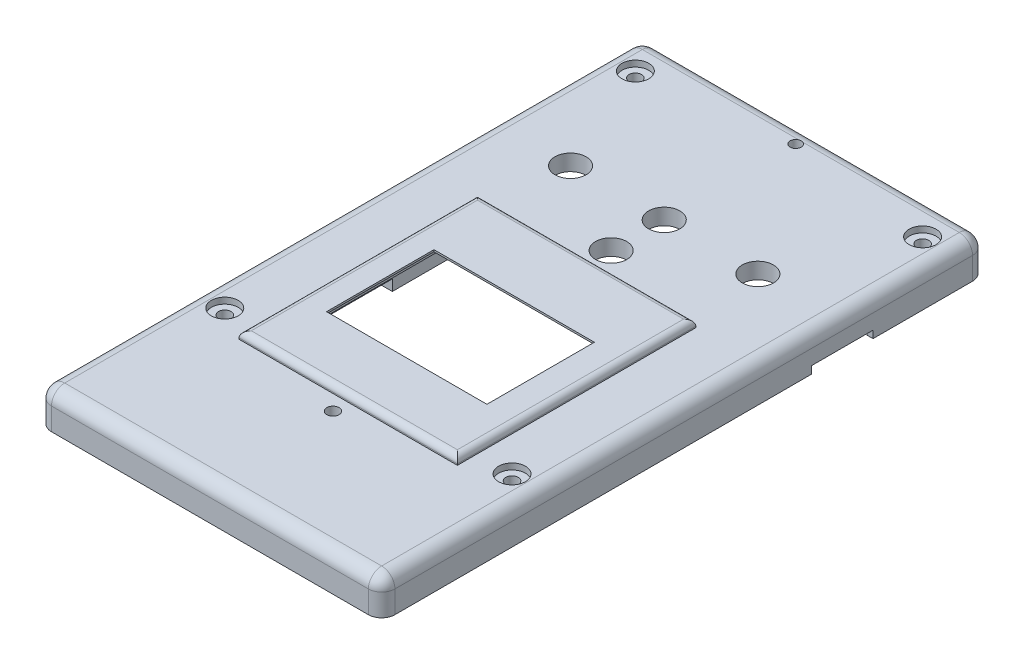
SolidWorks part; units mm, degrees
ref_plane "Face" through (0, 0, 0) normal (0, 0, 1) x (1, 0, 0)
ref_plane "Dessus" through (0, 0, 0) normal (0, 1, 0) x (1, 0, 0)
ref_plane "Droite" through (0, 0, 0) normal (1, 0, 0) x (0, 0, -1)
sketch "Sketch1" plane through (0, 0, 0) normal (0, 1, 0) x (1, 0, 0)
  line L0 (0, -49.53) -> (0, 0) construction
  line L1 (27.94, -49.53) -> (-27.94, -49.53)
  line L2 (27.94, -49.53) -> (27.94, 48.768)
  line L3 (27.94, 48.768) -> (-27.94, 48.768)
  line L4 (-27.94, -49.53) -> (-27.94, 48.768)
  point P0 (0, 0)
  dimension "D1" = 55.88
  dimension "D2" = 49.53
  dimension "D3" = 48.768
extrude "Boss-Extrude1" add sketch "Sketch1" along normal blind 4.99
fillet "Fillet1" radius 2.159 8 edges at (0, 4.99, 49.53) (27.94, 4.99, 0.381) (0, 4.99, -48.768) (-27.94, 4.99, 0.381) (-27.94, 2.495, -48.768) (27.94, 2.495, -48.768) (27.94, 2.495, 49.53) (-27.94, 2.495, 49.53)
sketch "Sketch3" plane through (0, 0, 0) normal (0, -1, 0) x (1, 0, 0)
  line L1 (21.6281, -38.862) -> (-20.4089, -38.862)
  line L2 (21.6281, -38.862) -> (21.6281, 26.576)
  line L3 (21.6281, 26.576) -> (-20.4089, 26.576)
  line L4 (-20.4089, -38.862) -> (-20.4089, 26.576)
  line L5 (21.6281, -38.862) -> (-20.4089, 26.576) construction
  line L6 (21.6281, 26.576) -> (-20.4089, -38.862) construction
  point P0 (0.6096, -6.143)
  dimension "D1" = 42.037
  dimension "D2" = 26.576
  dimension "D3" = 38.862
  dimension "D4" = 0.6096
sketch "Sketch7" plane through (0, 0, 0) normal (0, -1, 0) x (1, 0, 0)
  line L6 (-25.781, -47.752) -> (25.781, -47.752)
  line L9 (26.924, 47.371) -> (26.924, -46.609)
  line L10 (-26.924, -46.609) -> (-26.924, 47.371)
  line L11 (-25.781, 48.514) -> (25.781, 48.514)
  line L12 (26.924, 47.371) -> (26.924, -46.609)
  line L13 (-26.924, -46.609) -> (-26.924, 47.371)
  line L14 (-25.781, 48.514) -> (25.781, 48.514)
  arc A9 (25.781, -47.752) -> (26.924, -46.609) centre (25.781, -46.609) ccw
  arc A16 (25.781, -47.752) -> (26.924, -46.609) centre (25.781, -46.609) ccw
  arc A17 (-26.924, -46.609) -> (-25.781, -47.752) centre (-25.781, -46.609) ccw
  arc A18 (-26.924, -46.609) -> (-25.781, -47.752) centre (-25.781, -46.609) ccw
  arc A19 (-25.781, 48.514) -> (-26.924, 47.371) centre (-25.781, 47.371) ccw
  arc A20 (-25.781, 48.514) -> (-26.924, 47.371) centre (-25.781, 47.371) ccw
  arc A21 (26.924, 47.371) -> (25.781, 48.514) centre (25.781, 47.371) ccw
  arc A22 (26.924, 47.371) -> (25.781, 48.514) centre (25.781, 47.371) ccw
  dimension "D1" = 1.016
  dimension "D2" = 1.016
extrude "Cut-Extrude4" cut sketch "Sketch7" against normal blind 0.5874
sketch "Sketch8" plane through (0, 0, 0) normal (0, -1, 0) x (1, 0, 0)
  line L0 (27.94, 47.371) -> (27.94, -46.609) construction
  line L2 (26.924, -46.609) -> (26.924, 47.371) construction
  line L3 (-25.781, -47.752) -> (25.781, -47.752) construction
  line L4 (26.924, -46.609) -> (26.924, -40.386)
  line L5 (21.717, -47.752) -> (25.781, -47.752)
  line L6 (21.717, -47.752) -> (21.717, -40.386)
  line L7 (21.717, -40.386) -> (26.924, -40.386)
  circle A0 centre (23.4188, -43.006) radius 0.889
  arc A1 (25.781, -47.752) -> (26.924, -46.609) centre (25.781, -46.609) ccw construction
  arc A2 (25.781, -47.752) -> (26.924, -46.609) centre (25.781, -46.609) ccw
  dimension "D3" = 1.778
  dimension "D1" = 4.5212
  dimension "D2" = 43.006
  dimension "D4" = 6.223
  dimension "D5" = 40.386
sketch "Sketch9" plane through (0, 0, 0) normal (0, -1, 0) x (1, 0, 0)
  line L0 (-26.924, 47.371) -> (-26.924, -46.609) construction
  line L1 (-25.781, -47.752) -> (25.781, -47.752) construction
  line L2 (-26.924, -40.005) -> (-26.924, -46.609)
  line L3 (-25.781, -47.752) -> (-20.447, -47.752)
  line L4 (-20.447, -47.752) -> (-20.447, -40.005)
  line L5 (-20.447, -40.005) -> (-26.924, -40.005)
  line L6 (-27.94, -46.609) -> (-27.94, 47.371) construction
  arc A0 (-26.924, -46.609) -> (-25.781, -47.752) centre (-25.781, -46.609) ccw construction
  arc A1 (-26.924, -46.609) -> (-25.781, -47.752) centre (-25.781, -46.609) ccw
  circle A2 centre (-23.3172, -43.006) radius 0.889
  dimension "D5" = 1.778
  dimension "D1" = 7.493
  dimension "D2" = 43.006
  dimension "D3" = 3.6068
  dimension "D4" = 40.005
sketch "Sketch10" plane through (0, 0, 0) normal (0, -1, 0) x (1, 0, 0)
  line L0 (-27.94, -46.609) -> (-27.94, 47.371) construction
  line L1 (-26.924, 47.371) -> (-26.924, -46.609) construction
  line L2 (-26.924, 17.78) -> (-20.447, 17.78)
  line L3 (-26.924, 17.78) -> (-26.924, 26.67)
  line L4 (-26.924, 26.67) -> (-20.447, 26.67)
  line L5 (-20.447, 17.78) -> (-20.447, 26.67)
  circle A0 centre (-23.3172, 23.796) radius 0.889
  dimension "D6" = 1.778
  dimension "D1" = 4.6228
  dimension "D2" = 23.796
  dimension "D3" = 6.477
  dimension "D4" = 26.67
  dimension "D5" = 17.78
sketch "Sketch11" plane through (0, 0, 0) normal (0, -1, 0) x (1, 0, 0)
  line L0 (26.924, -46.609) -> (26.924, 47.371) construction
  line L1 (26.924, 27.686) -> (21.7502, 27.686)
  line L2 (26.924, 27.686) -> (26.924, 20.32)
  line L3 (26.924, 20.32) -> (21.7502, 20.32)
  line L4 (21.7502, 27.686) -> (21.7502, 20.32)
  circle A0 centre (23.4188, 23.796) radius 0.889
  dimension "D6" = 1.778
  dimension "D1" = 23.796
  dimension "D2" = 23.4188
  dimension "D3" = 27.686
  dimension "D4" = 20.32
  dimension "D5" = 21.7502
sketch "Sketch12" plane through (0, 0.5874, 0) normal (0, -1, 0) x (1, 0, 0)
  line L0 (26.924, -38.1) -> (19.812, -38.1)
  line L1 (-26.924, 27.94) -> (-16.28, 27.94)
  line L3 (-26.924, 13.7274) -> (-16.28, 13.7274)
  line L4 (26.924, -46.609) -> (26.924, 47.371)
  line L5 (25.781, 48.514) -> (-25.781, 48.514)
  line L6 (-26.924, 47.371) -> (-26.924, -46.609)
  line L7 (-25.781, -47.752) -> (25.781, -47.752)
  line L8 (26.924, -38.1) -> (26.924, -17.145)
  line L9 (25.781, 48.514) -> (8.5725, 48.514)
  line L10 (-26.924, 47.371) -> (-26.924, 27.94)
  line L11 (-19.812, -47.752) -> (19.812, -47.752)
  line L12 (-16.28, 27.94) -> (-16.28, 13.7274)
  line L13 (26.924, 27.94) -> (19.812, 27.94)
  line L17 (19.812, -38.1) -> (19.812, -47.752)
  line L18 (-26.924, -38.1) -> (-19.812, -38.1)
  line L19 (-19.812, -38.1) -> (-19.812, -47.752)
  line L20 (-26.924, 3.429) -> (-16.28, 3.429)
  line L21 (-16.28, 3.429) -> (-16.28, -17.145)
  line L22 (-16.28, -17.145) -> (-26.924, -17.145)
  line L25 (19.812, -17.145) -> (26.924, -17.145)
  line L26 (0, 44.704) -> (0, 0) construction
  line L28 (8.5725, 48.514) -> (8.5725, 44.704)
  line L29 (8.5725, 44.704) -> (-8.5725, 44.704)
  line L30 (-8.5725, 48.514) -> (-8.5725, 44.704)
  line L31 (0, 0) -> (0, -47.752) construction
  line L36 (-8.5725, 48.514) -> (-25.781, 48.514)
  line L37 (26.924, 27.94) -> (26.924, 47.371)
  line L38 (-26.924, 13.7274) -> (-26.924, 3.429)
  line L39 (-26.924, -17.145) -> (-26.924, -38.1)
  line L40 (26.924, -3.275) -> (26.924, 12.725)
  line L41 (19.812, -17.145) -> (19.812, -11.275)
  line L42 (19.812, -11.275) -> (22.346, -11.275)
  line L43 (22.346, -11.275) -> (22.346, -3.275)
  line L44 (22.346, -3.275) -> (26.924, -3.275)
  line L45 (19.812, 27.94) -> (19.812, 20.725)
  line L46 (19.812, 20.725) -> (22.346, 20.725)
  line L47 (22.346, 20.725) -> (22.346, 12.725)
  line L48 (22.346, 12.725) -> (26.924, 12.725)
  arc A4 (25.781, -47.752) -> (26.924, -46.609) centre (25.781, -46.609) ccw
  arc A5 (26.924, 47.371) -> (25.781, 48.514) centre (25.781, 47.371) ccw
  arc A6 (-25.781, 48.514) -> (-26.924, 47.371) centre (-25.781, 47.371) ccw
  arc A7 (-26.924, -46.609) -> (-25.781, -47.752) centre (-25.781, -46.609) ccw
  arc A9 (26.924, 47.371) -> (25.781, 48.514) centre (25.781, 47.371) ccw
  arc A10 (-25.781, 48.514) -> (-26.924, 47.371) centre (-25.781, 47.371) ccw
  line M33 (26.924, -46.609) -> (26.924, 47.371)
  arc M34 (26.924, 47.371) -> (25.781, 48.514) centre (25.781, 47.371) ccw
  line M35 (25.781, 48.514) -> (-25.781, 48.514)
  arc M36 (-25.781, 48.514) -> (-26.924, 47.371) centre (-25.781, 47.371) ccw
  line M37 (-26.924, 47.371) -> (-26.924, -46.609)
  line M39 (-25.781, -47.752) -> (25.781, -47.752)
  dimension "D2" = 12.725
  dimension "D3" = 17.145
  dimension "D4" = 3.81
  dimension "D5" = 27.94
  dimension "D6" = 14.2126
  dimension "D7" = 3.429
  dimension "D8" = 17.145
  dimension "D9" = 38.1
  dimension "D10" = 39.624
  dimension "D11" = 16.28
  dimension "D12" = 4.578
  dimension "D13" = 32
  dimension "D14" = 20.725
  dimension "D15" = 16
  dimension "D1" = 0
extrude "Cut-Extrude5" cut sketch "Sketch12" against normal blind 1.778 contours L17 L0 L25 L41 L48 L13 L28 L29 L30 L1 L12 L3 L20 L21 L22 L18 L19 M39 M33 M34 M35 M36 M37 region at (0.9045, 0.5874, 0.4828)
fillet "Fillet4" radius 1.016 11 edges at (26.924, 2.3654, 37.6555) (26.5892, 2.3654, 48.1792) (-26.924, 2.3654, 37.6555) (-26.5892, 2.3654, 48.1792) (0, 2.3654, -47.752) (-26.924, 2.3654, 8.5782) (-26.924, 2.3654, -27.6225) (26.924, 2.3654, -27.6225) (26.924, 2.3654, 4.725) (17.1767, 2.3654, 48.514) (-17.1767, 2.3654, 48.514)
hole_wizard "Chambrage pour vis à tête ronde à 6 pans creux #11" positions "Sketch13" profile "Sketch14" counterbore size "#1" standard "Ansi Inch"
sketch "Sketch13" plane through (0, 4.99, 0) normal (0, 1, 0) x (1, 0, 0)
  point P0 (-23.3172, -23.796)
  point P3 (23.4188, -23.796)
  point P6 (23.4188, 43.006)
  point P9 (-23.3172, 43.006)
sketch "Sketch14" plane through (-23.3172, 4.99, 23.796) normal (1, 0, 0) x (0, 0, 1)
  line L0 (0, 0) -> (0, 6.6105)
  line L1 (0, 6.6105) -> (1.016, 6)
  line L2 (1.016, 6) -> (1.016, 0.9906)
  line L3 (1.016, 0.9906) -> (2.1844, 0.9906)
  line L4 (2.1844, 0.9906) -> (2.1844, 0)
  line L5 (2.1844, 0) -> (0, 0)
  line L10 (0, 6.6105) -> (-1.016, 6) construction
  line L11 (0, -6.35) -> (0, 107.95) construction
  dimension "Diamètre du perçage" = 2.032
  dimension "Profondeur du perçage" = 6
  dimension "Diamètre du chambrage" = 4.3688
  dimension "Profondeur du chambrage" = 0.9906
  dimension "Angle de pointe" = 118
sketch "Sketch15" plane through (0, 2.3654, 0) normal (0, -1, 0) x (1, 0, 0)
  line L0 (0, 0) -> (0, -15.748) construction
  line L1 (0, -15.748) -> (0, -24.384) construction
  line L2 (0, -24.384) -> (-15.24, -24.384) construction
  line L3 (0, -24.384) -> (15.24, -24.384) construction
  circle A0 centre (0, -24.384) radius 2.54
  circle A1 centre (-15.24, -24.384) radius 2.54
  circle A2 centre (15.24, -24.384) radius 2.54
  circle A3 centre (0, -15.748) radius 2.54
  dimension "D4" = 5.08
  dimension "D1" = 24.384
  dimension "D2" = 15.748
  dimension "D3" = 30.48
extrude "Cut-Extrude6" cut sketch "Sketch15" against normal through all
sketch "Sketch16" plane through (0, 0.5874, 0) normal (0, 1, 0) x (1, 0, 0)
  line L0 (-25.781, -48.514) -> (-8.5725, -48.514) construction
  line L1 (16.424, -25.764) -> (-16.424, -25.764)
  line L2 (16.424, -25.764) -> (16.424, 11.236)
  line L3 (16.424, 11.236) -> (-16.424, 11.236)
  line L4 (-16.424, -25.764) -> (-16.424, 11.236)
  line L5 (26.924, 46.609) -> (26.924, -47.371) construction
  point P9 (0, 11.236)
  dimension "D1" = 22.75
  dimension "D2" = 10.5
  dimension "D3" = 37
extrude "Cut-Extrude7" cut sketch "Sketch16" along normal blind 4.2
sketch "Sketch17" plane through (0, 0, 0) normal (0, -1, 0) x (1, 0, 0)
  line L0 (-25.781, -47.752) -> (25.781, -47.752) construction
  line L1 (26.924, -46.609) -> (26.924, 47.371) construction
  line L2 (25.781, 48.514) -> (-25.781, 48.514) construction
  line L3 (-26.924, 47.371) -> (-26.924, -46.609) construction
  line L4 (-27.94, 47.371) -> (-27.94, -46.609)
  line L5 (-25.781, -48.768) -> (25.781, -48.768)
  line L6 (27.94, -46.609) -> (27.94, 47.371)
  line L7 (25.781, 49.53) -> (-25.781, 49.53)
  line L8 (-27.94, 47.371) -> (-27.94, -46.609)
  line L9 (-25.781, -48.768) -> (25.781, -48.768)
  line L10 (27.94, -46.609) -> (27.94, 47.371)
  line L11 (25.781, 49.53) -> (-25.781, 49.53)
  line L12 (-25.781, -47.752) -> (25.781, -47.752)
  line L13 (26.924, -46.609) -> (26.924, 47.371)
  line L14 (25.781, 48.514) -> (-25.781, 48.514)
  line L15 (-26.924, 47.371) -> (-26.924, -46.609)
  arc A0 (-26.924, -46.609) -> (-25.781, -47.752) centre (-25.781, -46.609) ccw construction
  arc A1 (25.781, -47.752) -> (26.924, -46.609) centre (25.781, -46.609) ccw construction
  arc A2 (26.924, 47.371) -> (25.781, 48.514) centre (25.781, 47.371) ccw construction
  arc A3 (-25.781, 48.514) -> (-26.924, 47.371) centre (-25.781, 47.371) ccw construction
  arc A4 (-27.94, -46.609) -> (-25.781, -48.768) centre (-25.781, -46.609) ccw
  arc A5 (25.781, -48.768) -> (27.94, -46.609) centre (25.781, -46.609) ccw
  arc A6 (27.94, 47.371) -> (25.781, 49.53) centre (25.781, 47.371) ccw
  arc A7 (-25.781, 49.53) -> (-27.94, 47.371) centre (-25.781, 47.371) ccw
  arc A8 (-27.94, -46.609) -> (-25.781, -48.768) centre (-25.781, -46.609) ccw
  arc A9 (25.781, -48.768) -> (27.94, -46.609) centre (25.781, -46.609) ccw
  arc A10 (27.94, 47.371) -> (25.781, 49.53) centre (25.781, 47.371) ccw
  arc A11 (-25.781, 49.53) -> (-27.94, 47.371) centre (-25.781, 47.371) ccw
  arc A12 (-26.924, -46.609) -> (-25.781, -47.752) centre (-25.781, -46.609) ccw
  arc A13 (25.781, -47.752) -> (26.924, -46.609) centre (25.781, -46.609) ccw
  arc A14 (26.924, 47.371) -> (25.781, 48.514) centre (25.781, 47.371) ccw
  arc A15 (-25.781, 48.514) -> (-26.924, 47.371) centre (-25.781, 47.371) ccw
  dimension "D1" = 0
extrude "Boss-Extrude2" add sketch "Sketch17" along normal blind 0.8
sketch "Esquisse19" plane through (0, 4.99, 0) normal (0, 1, 0) x (1, 0, 0)
  line L0 (-25.781, 48.768) -> (25.781, 48.768) construction
  line L1 (17.765, 11.768) -> (-17.765, 11.768)
  line L2 (17.765, 11.768) -> (17.765, -27.03)
  line L3 (17.765, -27.03) -> (-17.765, -27.03)
  line L4 (-17.765, 11.768) -> (-17.765, -27.03)
  line L5 (-27.94, -47.371) -> (-27.94, 46.609) construction
  line L6 (27.94, 46.609) -> (27.94, -47.371) construction
  line L7 (25.781, -49.53) -> (-25.781, -49.53) construction
  dimension "D1" = 37
  dimension "D2" = 10.175
  dimension "D3" = 10.175
  dimension "D4" = 22.5
extrude "Boss.-Extru.2" add sketch "Esquisse19" along normal blind 1.2
sketch "Esquisse1" plane through (0, 4.99, 0) normal (0, 1, 0) x (1, 0, 0)
  line L0 (25.781, -48.514) -> (-25.781, -48.514) construction
  circle A0 centre (0, -29.514) radius 1
  dimension "D1" = 19
  dimension "D2" = 2
extrude "Enlèv. mat.-Extru.1" cut sketch "Esquisse1" against normal through all
sketch "Esquisse5" plane through (27.94, 0, 0) normal (1, 0, 0) x (0, 0, -1)
  line L0 (46.609, -0.8) -> (-47.371, -0.8) construction
  line L1 (30.418, -0.8) -> (20.418, -0.8)
  line L2 (30.418, -0.8) -> (30.418, 0.4)
  line L3 (30.418, 0.4) -> (20.418, 0.4)
  line L4 (20.418, -0.8) -> (20.418, 0.4)
  line L5 (48.768, 2.831) -> (48.768, -0.8) construction
  dimension "D1" = 18.35
  dimension "D2" = 10
  dimension "D3" = 1.2
extrude "Enlèv. mat.-Extru.3" cut sketch "Esquisse5" against normal blind 2
sketch "Esquisse13" plane through (0, 4.7874, 0) normal (0, -1, 0) x (1, 0, 0)
  line L0 (16.424, -11.236) -> (16.424, 25.764) construction
  line L1 (-14.124, 23.914) -> (13.624, 23.914)
  line L2 (-14.124, 23.914) -> (-14.124, -7.236)
  line L3 (-14.124, -7.236) -> (13.624, -7.236)
  line L4 (13.624, 23.914) -> (13.624, -7.236)
  line L5 (-16.424, 25.764) -> (16.424, 25.764) construction
  line L8 (-16.28, -11.236) -> (16.424, -11.236) construction
  line L9 (-16.424, -11.236) -> (-16.424, 25.764) construction
  dimension "D1" = 2.8
  dimension "D2" = 2.3
  dimension "D3" = 1.85
  dimension "D4" = 4
extrude "Enlèv. mat.-Extru.6" cut sketch "Esquisse13" against normal blind 1.1
sketch "Esquisse14" plane through (0, 4.99, 0) normal (0, 1, 0) x (1, 0, 0)
  line L4 (25.781, -47.371) -> (25.781, 46.609) construction
  circle A0 centre (0, 45.768) radius 0.9
  dimension "D1" = 1.8
  dimension "D2" = 25.781
extrude "Enlèv. mat.-Extru.7" cut sketch "Esquisse14" against normal blind 10
sketch "Esquisse15" plane through (0, 0, -48.768) normal (0, 0, -1) x (-1, 0, 0)
  line L0 (25.781, -0.8) -> (-25.781, -0.8) construction
  line L1 (19.85, -0.8) -> (7.91, -0.8)
  line L2 (19.85, -0.8) -> (19.85, -0.7)
  line L3 (19.85, -0.7) -> (7.91, -0.7)
  line L4 (7.91, -0.8) -> (7.91, -0.7)
  line L5 (27.94, 2.831) -> (27.94, -0.8) construction
  dimension "D1" = 8.09
  dimension "D2" = 11.94
  dimension "D3" = 0.1
extrude "Enlèv. mat.-Extru.8" cut sketch "Esquisse15" against normal up to next
chamfer "Chanfrein1" distance 1 angle 50 1 edges at (-13.88, -0.7, -48.768) first distance on face at (-6.94, 0.1327, -48.768)
sketch "Esquisse16" plane through (0, 0, -48.768) normal (0, 0, -1) x (-1, 0, 0)
  line L0 (7.91, -0.8) -> (-25.781, -0.8) construction
  line L1 (-18.76, -0.8) -> (-6.95, -0.8)
  line L2 (-18.76, -0.8) -> (-18.76, -0.3)
  line L3 (-18.76, -0.3) -> (-6.95, -0.3)
  line L4 (-6.95, -0.8) -> (-6.95, -0.3)
  line L5 (-27.94, -0.8) -> (-27.94, 2.831) construction
  dimension "D1" = 20.99
  dimension "D2" = 9.18
  dimension "D3" = 0.5
extrude "Enlèv. mat.-Extru.9" cut sketch "Esquisse16" against normal up to next
sketch "Esquisse17" plane through (0, 0, -48.768) normal (0, 0, -1) x (-1, 0, 0)
  line L0 (7.91, -0.8) -> (-6.95, -0.8) construction
  line L1 (-4.5, -0.8) -> (4.5, -0.8)
  line L2 (-4.5, -0.8) -> (-4.5, 0)
  line L3 (-4.5, 0) -> (4.5, 0)
  line L4 (4.5, -0.8) -> (4.5, 0)
  line L5 (-27.94, -0.8) -> (-27.94, 2.831) construction
  line L6 (27.94, 2.831) -> (27.94, -0.8) construction
  dimension "D1" = 23.44
  dimension "D2" = 23.44
  dimension "D3" = 0.8
extrude "Enlèv. mat.-Extru.10" cut sketch "Esquisse17" against normal blind 10
sketch "Esquisse18" plane through (0, 0, -48.768) normal (0, 0, -1) x (-1, 0, 0)
  line L0 (-4.5, -0.8) -> (-5, -0.8)
  line L1 (-4.5, -0.8) -> (-6.95, -0.8) construction
  line L2 (-5, -0.8) -> (-5, 0.5)
  line L3 (-5, 0.5) -> (5, 0.5)
  line L4 (5, 0.5) -> (5, -0.8)
  line L5 (7.91, -0.8) -> (4.5, -0.8) construction
  line L6 (5, -0.8) -> (4.5, -0.8)
  line L7 (4.5, -0.8) -> (4.5, 0)
  line L8 (4.5, 0) -> (-4.5, 0)
  line L9 (-4.5, 0) -> (-4.5, -0.8)
  dimension "D1" = 0.5
  dimension "D2" = 0.5
  dimension "D3" = 0.5
extrude "Boss.-Extru.1" add sketch "Esquisse18" along normal blind 1.1
fillet "Congé1" radius 0.2 3 edges at (5, -0.15, -49.868) (0, 0.5, -49.868) (-5, -0.15, -49.868)
sketch "Esquisse12" plane through (0, 4.7874, 0) normal (0, 1, 0) x (1, 0, 0)
  line L1 (-13.334, 0.256) -> (12.764, 0.256)
  line L2 (-13.334, 0.256) -> (-13.334, -17.224)
  line L3 (-13.334, -17.224) -> (12.764, -17.224)
  line L4 (12.764, 0.256) -> (12.764, -17.224)
  line L8 (-14.124, -23.914) -> (-14.124, 7.236) construction
  line L9 (-14.124, 7.236) -> (13.624, 7.236) construction
  line L10 (13.624, 7.236) -> (13.624, -23.914) construction
  line L11 (13.624, -23.914) -> (-14.124, -23.914) construction
  dimension "D1" = 0.79
  dimension "D2" = 6.98
  dimension "D3" = 6.69
  dimension "D4" = 0.86
extrude "Enlèv. mat.-Extru.5" cut sketch "Esquisse12" along normal blind 22
fillet "Congé2" radius 1 4 edges at (0, 6.19, 27.03) (-17.765, 6.19, 7.631) (0, 6.19, -11.768) (17.765, 6.19, 7.631)
